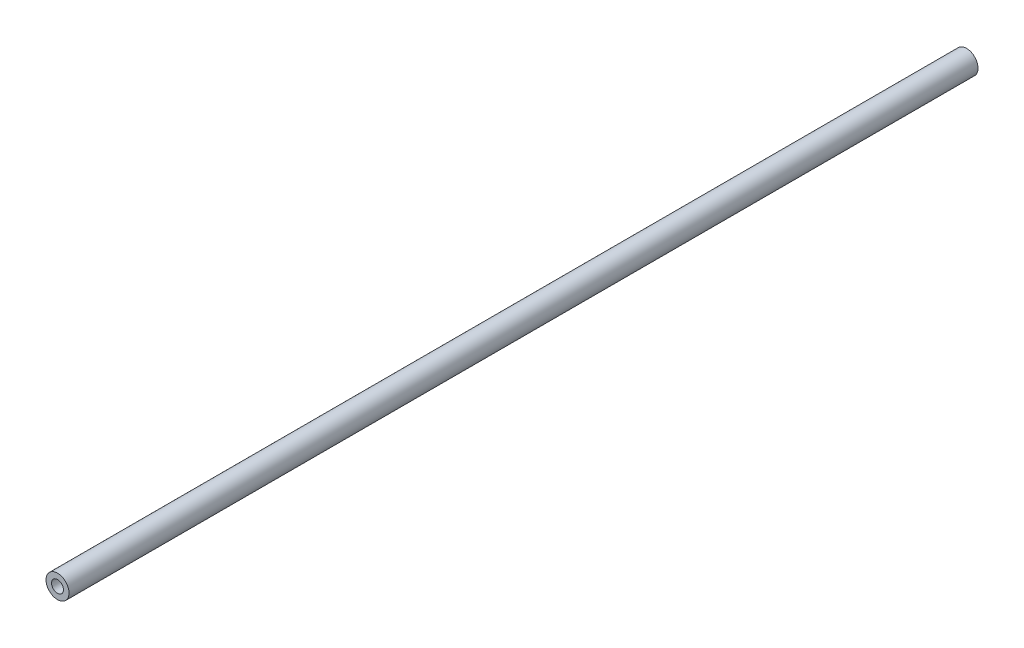
SolidWorks part; units mm, degrees
material "Plain Carbon Steel"
ref_plane "Front Plane" through (0, 0, 0) normal (0, 0, 1) x (1, 0, 0)
ref_plane "Top Plane" through (0, 0, 0) normal (0, 1, 0) x (1, 0, 0)
ref_plane "Right Plane" through (0, 0, 0) normal (1, 0, 0) x (0, 0, -1)
sketch "Sketch1" plane through (0, 0, 0) normal (0, 0, 1) x (1, 0, 0)
  circle A0 centre (0, 0) radius 5
  dimension "D1" = 10
extrude "Boss-Extrude1" add sketch "Sketch1" along normal blind 395
hole_wizard "#6 (0.204) Diameter Hole1" positions "Sketch2" profile "Sketch3" hole size "#6" standard "ANSI Inch"
sketch "Sketch2" plane through (0, 0, 0) normal (0, 0, -1) x (-1, 0, 0)
  point P0 (0, 0)
sketch "Sketch3" plane through (0, 0, 0) normal (1, 0, 0) x (0, 1, 0)
  line L0 (0, 0) -> (0, 31.5567)
  line L1 (0, 31.5567) -> (2.5908, 30)
  line L2 (2.5908, 30) -> (2.5908, 0)
  line L5 (2.5908, 0) -> (0, 0)
  line L10 (0, 31.5567) -> (-2.5908, 30) construction
  line L11 (0, -6.35) -> (0, 107.95) construction
  dimension "Hole Dia." = 5.1816
  dimension "Hole Depth" = 30
  dimension "Drill Angle" = 118
hole_wizard "#6 (0.204) Diameter Hole2" positions "Sketch4" profile "Sketch5" hole size "#6" standard "ANSI Inch"
sketch "Sketch4" plane through (0, 0, 395) normal (0, 0, 1) x (1, 0, 0)
  point P0 (0, 0)
sketch "Sketch5" plane through (0, 0, 395) normal (1, 0, 0) x (0, -1, 0)
  line L0 (0, 0) -> (0, 31.5567)
  line L1 (0, 31.5567) -> (2.5908, 30)
  line L2 (2.5908, 30) -> (2.5908, 0)
  line L5 (2.5908, 0) -> (0, 0)
  line L10 (0, 31.5567) -> (-2.5908, 30) construction
  line L11 (0, -6.35) -> (0, 107.95) construction
  dimension "Hole Dia." = 5.1816
  dimension "Hole Depth" = 30
  dimension "Drill Angle" = 118
